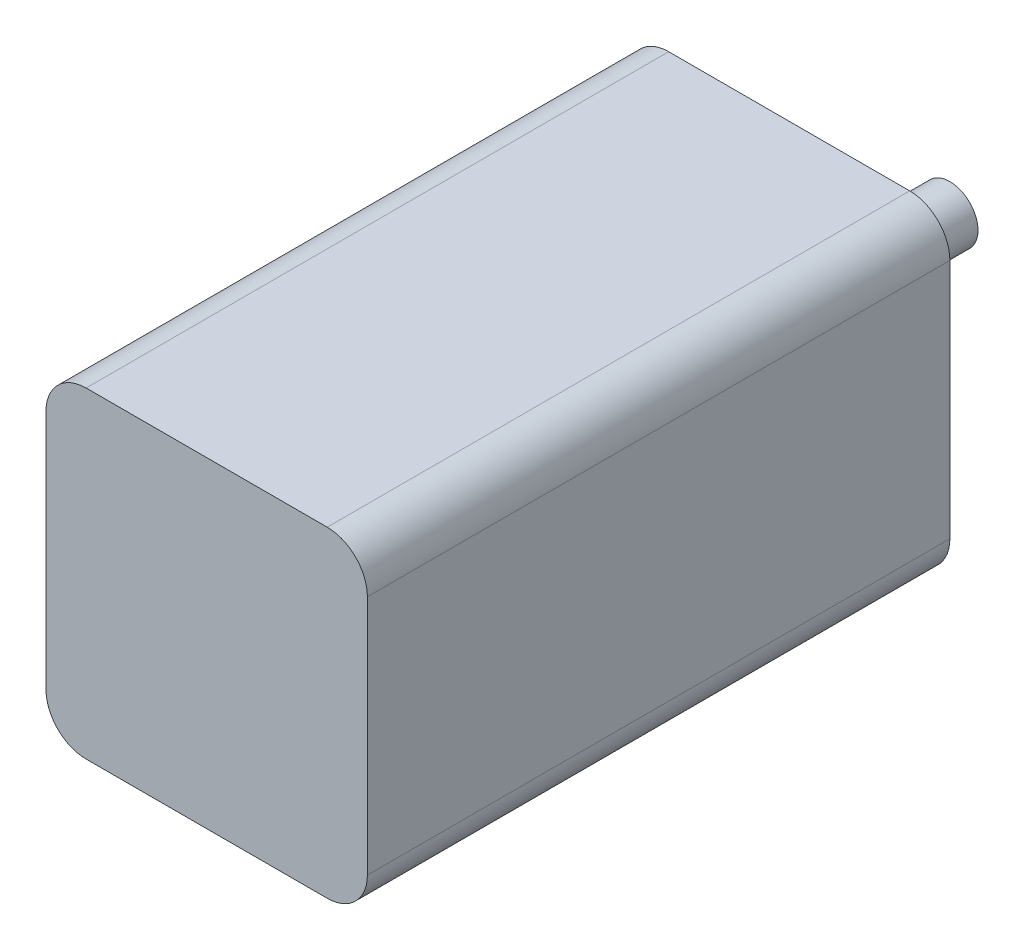
SolidWorks part; units mm, degrees
ref_plane "Front" through (0, 0, 0) normal (0, 0, 1) x (1, 0, 0)
ref_plane "Top" through (0, 0, 0) normal (0, 1, 0) x (1, 0, 0)
ref_plane "Right" through (0, 0, 0) normal (1, 0, 0) x (0, 0, -1)
other "Configuration Table"
sketch "Эскиз1" plane through (0, 0, 0) normal (0, 0, 1) x (1, 0, 0)
  line L1 (-56.4847, 18.7789) -> (23.5153, 18.7789)
  line L2 (-56.4847, 18.7789) -> (-56.4847, -61.2211)
  line L3 (-56.4847, -61.2211) -> (23.5153, -61.2211)
  line L4 (23.5153, 18.7789) -> (23.5153, -61.2211)
  dimension "D1" = 80
  dimension "D2" = 80
extrude "Бобышка-Вытянуть1" add sketch "Эскиз1" along normal blind 145
fillet "Скругление1" radius 10 4 edges at (-56.4847, -61.2211, 72.5) (23.5153, -61.2211, 72.5) (-56.4847, 18.7789, 72.5) (23.5153, 18.7789, 72.5)
sketch "Эскиз2" plane through (0, 0, 0) normal (0, 0, -1) x (-1, 0, 0)
  line L0 (56.4847, 8.7789) -> (56.4847, -51.2211) construction
  line L1 (-13.5153, 18.7789) -> (46.4847, 18.7789) construction
  circle A0 centre (16.4847, -21.2211) radius 7
  dimension "D1" = 40
  dimension "D2" = 40
extrude "Бобышка-Вытянуть2" add sketch "Эскиз2" along normal blind 40
